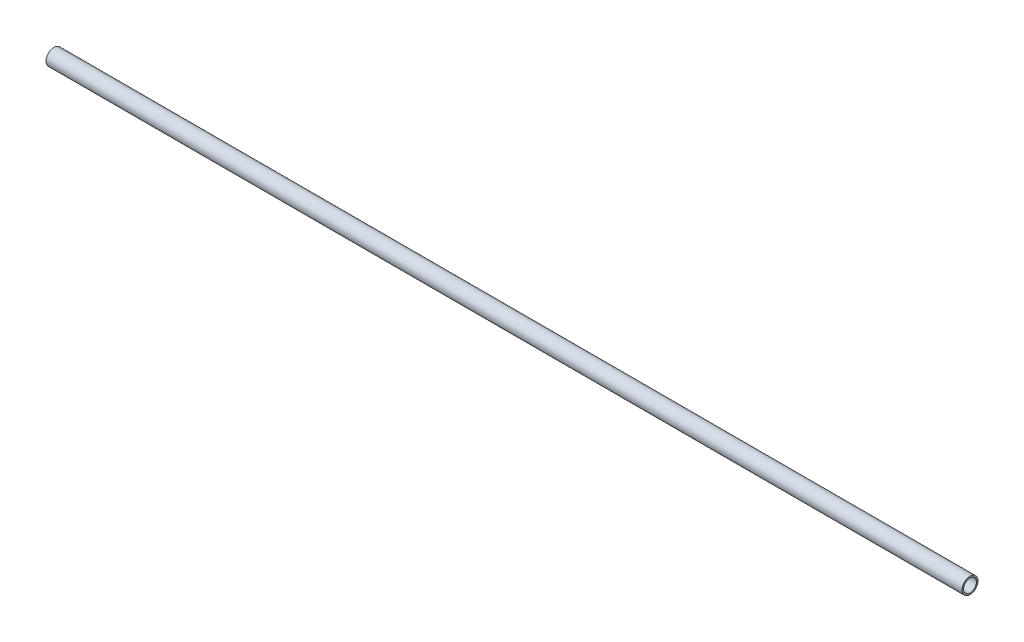
SolidWorks part; units mm, degrees
note: '?' marks a value the reader was unsure of.
material "Hexcel AS4C (3000 Filaments)"
ref_plane "Front Plane" through (0, 0, 0) normal (0, 0, 1) x (1, 0, 0)
ref_plane "Top Plane" through (0, 0, 0) normal (0, 1, 0) x (1, 0, 0)
ref_plane "Right Plane" through (0, 0, 0) normal (1, 0, 0) x (0, 0, -1)
sketch "Sketch1" plane through (0, 0, 0) normal (1, 0, 0) x (0, 0, -1)
  circle A0 centre (0, 0) radius 3.7592
  circle A1 centre (0, 0) radius 3.048
  dimension "D1" = 7.5184
  dimension "D2" = 0.7112
extrude "Boss-Extrude1" add sketch "Sketch1" along normal blind 215.9 and the other way blind 215.9
ref_point "Point1"
ref_axis "Axis1" through (0, 0, 13.9308) along (0, 0, -1)?
